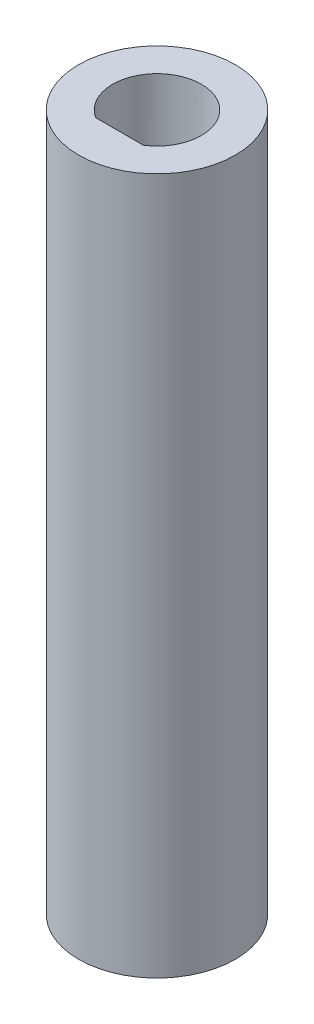
SolidWorks part; units mm, degrees
ref_plane "Front Plane" through (0, 0, 0) normal (0, 0, 1) x (1, 0, 0)
ref_plane "Top Plane" through (0, 0, 0) normal (0, 1, 0) x (1, 0, 0)
ref_plane "Right Plane" through (0, 0, 0) normal (1, 0, 0) x (0, 0, -1)
sketch "Sketch1" plane through (0, 0, 0) normal (0, 1, 0) x (1, 0, 0)
  line L0 (0, 0) -> (0, -3.2385) construction
  line L1 (0, 0) -> (3.2385, 0) construction
  line L2 (0, -2.7305) -> (1.7413, -2.7305) construction
  line L3 (1.7413, -2.7305) -> (-1.7413, -2.7305)
  circle A0 centre (0, 0) radius 3.2385 construction
  arc A1 (1.7413, -2.7305) -> (-1.7413, -2.7305) centre (0, 0) ccw
  circle A2 centre (0, 0) radius 5.715
  dimension "D1" = 6.477
  dimension "D3" = 11.43
  dimension "D2" = 0.508
extrude "Boss-Extrude1" add sketch "Sketch1" along normal blind 12.7
sketch "Sketch3" plane through (0, 0, 0) normal (0, -1, 0) x (-1, 0, 0)
  circle A0 centre (0, 0) radius 5.715
extrude "Boss-Extrude2" add sketch "Sketch3" along normal blind 38.1
sketch "Sketch4" plane through (0, -38.1, 0) normal (0, -1, 0) x (1, 0, 0)
  line L0 (0, 2.54) -> (-1.7961, 4.3361)
  line L1 (-2.54, -2.54) -> (2.54, -2.54) construction
  line L2 (-2.54, -2.54) -> (-2.54, 2.54) construction
  line L3 (-2.54, 2.54) -> (2.54, 2.54) construction
  line L4 (2.54, -2.54) -> (2.54, 2.54) construction
  line L5 (-2.54, -2.54) -> (2.54, 2.54) construction
  line L6 (-2.54, 2.54) -> (2.54, -2.54) construction
  line L7 (-2.54, 0) -> (-4.3361, 1.7961)
  line L8 (-4.3361, 1.7961) -> (-1.7961, 4.3361)
  line L9 (2.54, 0) -> (4.3361, -1.7961)
  line L10 (0, -2.54) -> (1.7961, -4.3361)
  line L11 (1.7961, -4.3361) -> (4.3361, -1.7961)
  line L12 (-2.54, 0) -> (-4.3361, -1.7961)
  line L13 (0, -2.54) -> (-1.7961, -4.3361)
  line L14 (-4.3361, -1.7961) -> (-1.7961, -4.3361)
  line L15 (2.54, 0) -> (4.3361, 1.7961)
  line L16 (1.7961, 4.3361) -> (4.3361, 1.7961)
  line L17 (0, 2.54) -> (1.7961, 4.3361)
  point P0 (0, 0)
  dimension "D1" = 2.54
  dimension "D2" = 5.08
  dimension "D3" = 5.08
  dimension "D4" = 8.6721
  dimension "D5" = 3.5921
  dimension "D6" = 3.5921
  dimension "D7" = 3.5921
  dimension "D8" = 3.5921
  dimension "D9" = 8.6721
  dimension "D10" = 0
  dimension "D11" = 3.5921
  dimension "D12" = 5.08
  dimension "D13" = 2.54
  dimension "D14" = 2.54
  dimension "D15" = 2.54
  dimension "D16" = 2.54
  dimension "D17" = 2.54
  dimension "D18" = 2.54
  dimension "D19" = 2.54
  dimension "D20" = 2.54
extrude "Cut-Extrude1" cut sketch "Sketch4" against normal blind 38.1
